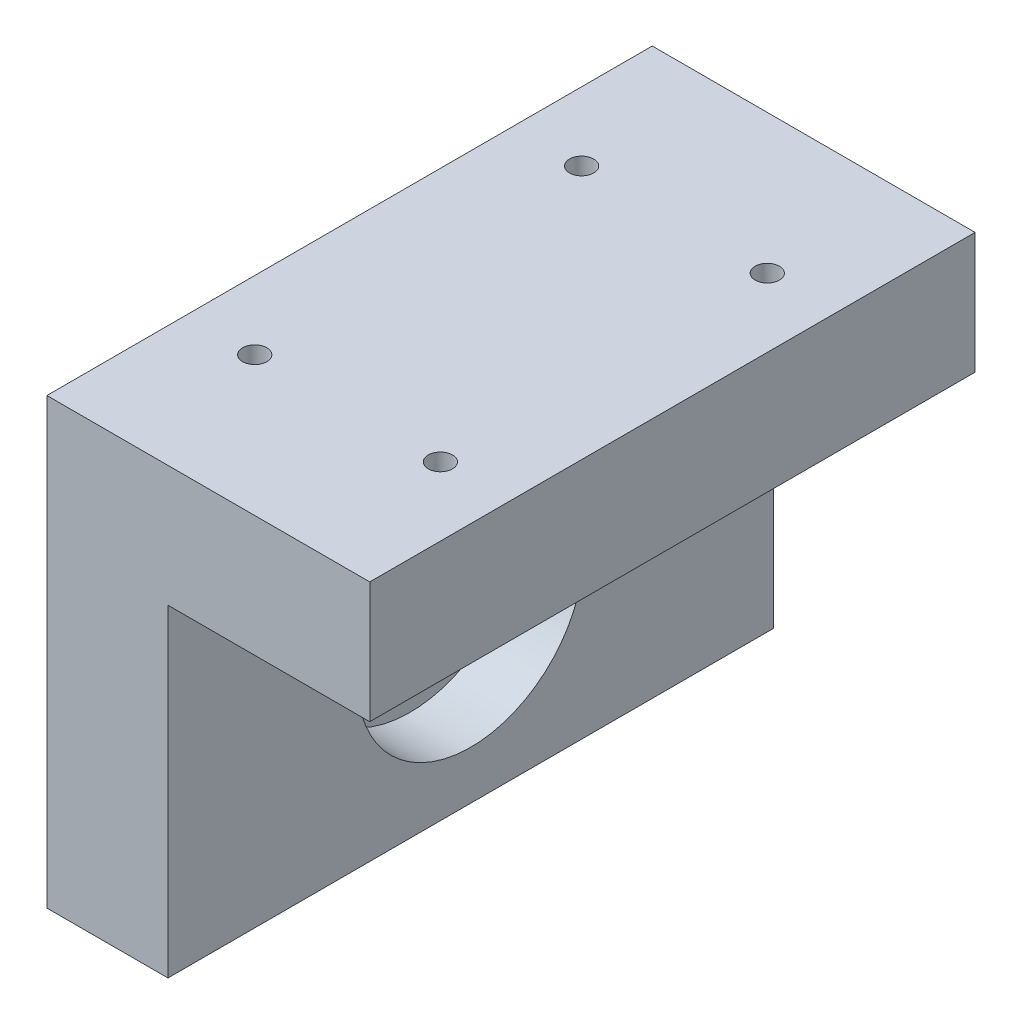
SolidWorks part; units mm, degrees
ref_plane "Front Plane" through (0, 0, 0) normal (0, 0, 1) x (1, 0, 0)
ref_plane "Top Plane" through (0, 0, 0) normal (0, 1, 0) x (1, 0, 0)
ref_plane "Right Plane" through (0, 0, 0) normal (1, 0, 0) x (0, 0, -1)
sketch "Sketch1" plane through (0, 0, 0) normal (1, 0, 0) x (0, 0, -1)
  line L0 (-37.5, 40) -> (-37.5, 0) construction
  line L1 (0, 0) -> (-75, 0)
  line L2 (0, 0) -> (0, 40)
  line L3 (0, 40) -> (-75, 40)
  line L4 (-75, 0) -> (-75, 40)
  circle A1 centre (-37.5, 20) radius 14
  circle A2 centre (-37.5, 20) radius 3
  point P10 (-75, 0)
  dimension "D1" = 28
  dimension "D3" = 6
  dimension "D2" = 40
  dimension "D4" = 75
extrude "Boss-Extrude1" add sketch "Sketch1" along normal blind 15 contours L0 L3 L4 L1 A1 | L3 L0 A1 L1 L2 region at (0, 20, 15.4422) region at (0, 20, 59.5578)
extrude "Boss-Extrude2" add sketch "Sketch1<3>" along normal blind 7.5 contours L0 A1 A2 | A1 L0 A2 region at (0, 20, 31.3335) region at (0, 20, 43.6665)
sketch "Sketch1<3>" plane through (0, 0, 0) normal (1, 0, 0) x (0, 0, -1) same geometry as "Sketch1"
sketch "Sketch3" plane through (0, 40, 0) normal (0, 1, 0) x (1, 0, 0)
  line L0 (0, 0) -> (8.5, 0) construction
  line L1 (0, 0) -> (40, 0)
  line L2 (0, 0) -> (0, -75)
  line L3 (0, -75) -> (40, -75)
  line L4 (40, 0) -> (40, -75)
  line L5 (40, 0) -> (8.5, 0) construction
  line L6 (40, 0) -> (31.5, 0) construction
  line L7 (8.5, 0) -> (8.5, -17.25) construction
  line L8 (31.5, 0) -> (31.5, -17.25) construction
  line L9 (0, -37.5) -> (40, -37.5) construction
  line L10 (31.5, -75) -> (31.5, -57.75) construction
  line L11 (8.5, -75) -> (8.5, -57.75) construction
  circle A0 centre (8.5, -17.25) radius 1.5
  circle A1 centre (31.5, -17.25) radius 1.5
  circle A2 centre (31.5, -57.75) radius 1.5
  circle A3 centre (8.5, -57.75) radius 1.5
  dimension "D3" = 3
  dimension "D4" = 3
  dimension "D1" = 40
  dimension "D2" = 75
extrude "Boss-Extrude3" add sketch "Sketch3" along normal blind 15
